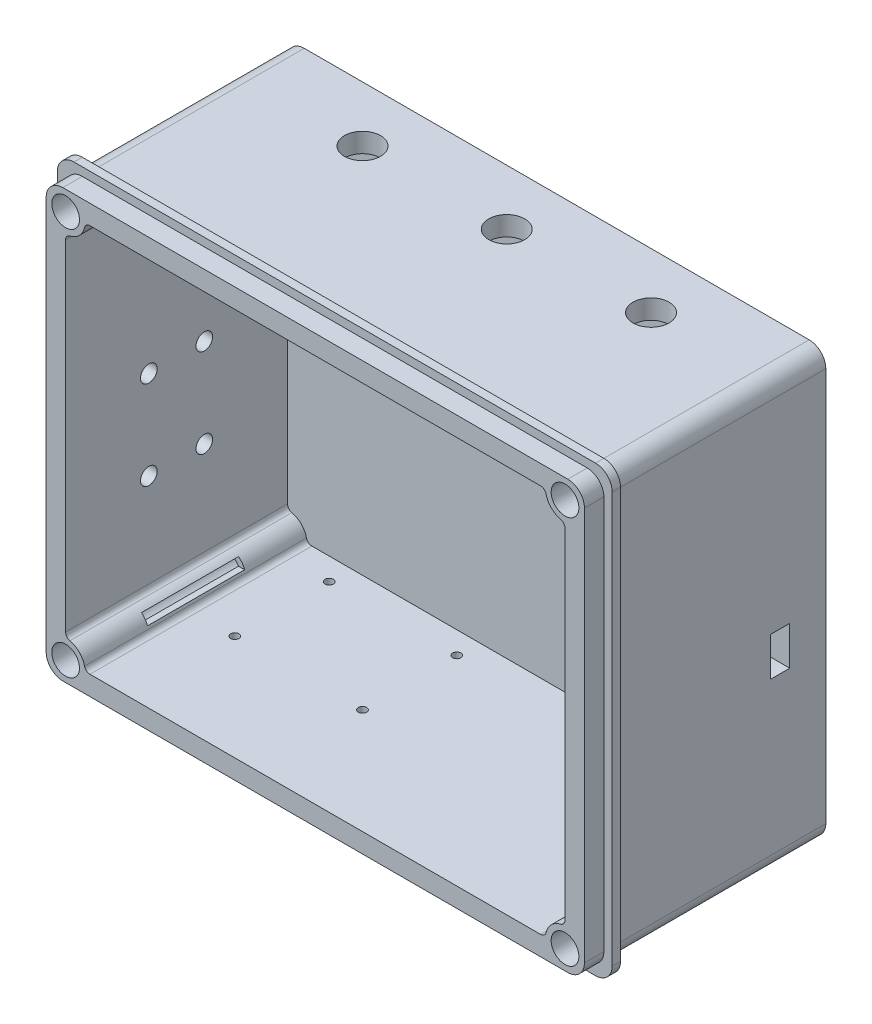
SolidWorks part; units mm, degrees
ref_plane "Plan de face" through (0, 0, 0) normal (0, 0, 1) x (1, 0, 0)
ref_plane "Plan de dessus" through (0, 0, 0) normal (0, 1, 0) x (1, 0, 0)
ref_plane "Plan de droite" through (0, 0, 0) normal (1, 0, 0) x (0, 0, -1)
sketch "Esquisse1" plane through (0, 0, 0) normal (0, 0, 1) x (1, 0, 0)
  line L1 (-90, -70) -> (90, -70)
  line L2 (-90, -70) -> (-90, 70)
  line L3 (-90, 70) -> (90, 70)
  line L4 (90, -70) -> (90, 70)
  line L5 (-90, -70) -> (90, 70) construction
  line L6 (-90, 70) -> (90, -70) construction
  line L7 (-91, -77) -> (91, -77)
  line L8 (-97, -71) -> (-97, 71)
  line L9 (-91, 77) -> (91, 77)
  line L10 (97, -71) -> (97, 71)
  line L11 (-97, -77) -> (97, 77) construction
  line L12 (-97, 77) -> (97, -77) construction
  arc A0 (91, 77) -> (97, 71) centre (91, 71) cw
  arc A1 (91, -77) -> (97, -71) centre (91, -71) ccw
  arc A2 (-91, -77) -> (-97, -71) centre (-91, -71) cw
  arc A3 (-97, 71) -> (-91, 77) centre (-91, 71) cw
  circle A7 centre (90, -70) radius 5
  circle A8 centre (90, 70) radius 5
  circle A9 centre (-90, 70) radius 5
  circle A10 centre (-90, -70) radius 5
  arc A11 (-83, 70) -> (-90, 63) centre (-90, 70) cw
  arc A12 (83, 70) -> (90, 63) centre (90, 70) ccw
  arc A13 (90, -63) -> (83, -70) centre (90, -70) ccw
  arc A14 (-90, -63) -> (-83, -70) centre (-90, -70) cw
  point P0 (0, 0)
  point P6 (0, 0)
  dimension "D5" = 6
  dimension "D6" = 10
  dimension "D7" = 10
  dimension "D8" = 10
  dimension "D9" = 10
  dimension "D10" = 2
  dimension "D11" = 2
  dimension "D12" = 2
  dimension "D13" = 2
  dimension "D1" = 180
  dimension "D2" = 140
  dimension "D3" = 7
  dimension "D4" = 7
extrude "Boss.-Extru.1" add sketch "Esquisse1" against normal blind 7 contours L2 A14 L1 A13 L4 A12 L3 A11 | A3 L8 A2 L7 A1 L10 A0 L9 A10 L2 A9 L3 A8 L4 A7 L1 | A11 L3 A9 L2 | A14 L2 A10 L1 | L4 A13 L1 A7 | L3 A12 L4 A8 region at (-86.1449, -66.1449, 0) region at (0, 0, 0) region at (86.1449, -66.1449, 0) region at (-86.1449, 66.1449, 0) region at (86.1449, 66.1449, 0) region at (-95.0675, -75.0675, 0)
extrude "Boss.-Extru.2" add sketch "Esquisse1<4>" along normal blind 80 contours A11 L3 A9 L2 | A3 L8 A2 L7 A1 L10 A0 L9 A10 L2 A9 L3 A8 L4 A7 L1 | A14 L2 A10 L1 | L4 A13 L1 A7 | L3 A12 L4 A8 region at (-86.1449, -66.1449, 0) region at (86.1449, -66.1449, 0) region at (-86.1449, 66.1449, 0) region at (86.1449, 66.1449, 0) region at (-95.0675, -75.0675, 0)
sketch "Esquisse1<4>" plane through (0, 0, 0) normal (0, 0, 1) x (1, 0, 0) same geometry as "Esquisse1"
fillet "Congé1" radius 2 8 edges at (-90, -63, 40) (-83, -70, 40) (90, -63, 40) (83, -70, 40) (90, 63, 40) (83, 70, 40) (-90, 63, 40) (-83, 70, 40)
sketch "Esquisse2" plane through (0, 0, 0) normal (0, 0, 1) x (1, 0, 0)
  line L0 (90, -61.225) -> (90, 61.225) construction
  line L1 (38, 67) -> (70, 67) construction
  line L2 (38, 67) -> (38, 25) construction
  line L3 (38, 25) -> (70, 25) construction
  line L4 (70, 67) -> (70, 25) construction
  line L5 (-81.225, 70) -> (81.225, 70) construction
  line L6 (41.5, 63.5) -> (66.5, 63.5) construction
  line L7 (41.5, 63.5) -> (41.5, 28.5) construction
  line L8 (41.5, 28.5) -> (66.5, 28.5) construction
  line L9 (66.5, 63.5) -> (66.5, 28.5) construction
  line L10 (28, 90.6353) -> (28, -84.2321) construction
  line L11 (-14, 67) -> (-14, 25) construction
  line L12 (-24, 90.6353) -> (-24, -84.2321) construction
  line L14 (49, 5) -> (87, 5) construction
  line L15 (49, 5) -> (49, -23) construction
  line L16 (49, -23) -> (87, -23) construction
  line L17 (87, 5) -> (87, -23) construction
  line L18 (52.5, 1.5) -> (83.5, 1.5) construction
  line L19 (52.5, 1.5) -> (52.5, -19.5) construction
  line L20 (52.5, -19.5) -> (83.5, -19.5) construction
  line L21 (83.5, 1.5) -> (83.5, -19.5) construction
  circle A0 centre (66.5, 28.5) radius 1.5
  circle A1 centre (66.5, 63.5) radius 1.5
  circle A2 centre (41.5, 63.5) radius 1.5
  circle A3 centre (41.5, 28.5) radius 1.5
  circle A4 centre (-10.5, 28.5) radius 1.5
  circle A5 centre (14.5, 28.5) radius 1.5
  circle A6 centre (-10.5, 63.5) radius 1.5
  circle A7 centre (14.5, 63.5) radius 1.5
  circle A8 centre (-62.5, 28.5) radius 1.5
  circle A9 centre (-37.5, 28.5) radius 1.5
  circle A10 centre (-62.5, 63.5) radius 1.5
  circle A11 centre (-37.5, 63.5) radius 1.5
  circle A12 centre (52.5, 1.5) radius 1.5
  circle A13 centre (83.5, 1.5) radius 1.5
  circle A14 centre (52.5, -19.5) radius 1.5
  circle A15 centre (83.5, -19.5) radius 1.5
  point P30 (-14, 46)
  dimension "D9" = 3
  dimension "D1" = 42
  dimension "D2" = 32
  dimension "D3" = 20
  dimension "D4" = 3.5
  dimension "D5" = 3.5
  dimension "D6" = 3.5
  dimension "D7" = 3.5
  dimension "D8" = 3
  dimension "D10" = 10
  dimension "D11" = 10
  dimension "D12" = 38
  dimension "D13" = 28
  dimension "D14" = 3.5
  dimension "D15" = 3.5
  dimension "D16" = 3.5
  dimension "D17" = 3.5
  dimension "D18" = 3
  dimension "D19" = 20
extrude "Enlèv. mat.-Extru.1" cut sketch "Esquisse2" against normal blind 80
sketch "Esquisse4" plane through (0, 77, 0) normal (0, 1, 0) x (1, 0, 0)
  line L0 (-66, 12.9423) -> (-66, -94.7228) construction
  line L1 (-50, 12.9423) -> (-50, -94.7228) construction
  line L2 (-34, 11.688) -> (-34, -94.7228) construction
  line L4 (-24, 11.688) -> (-24, -94.7228) construction
  line L5 (-91, 7) -> (91, 7) construction
  line L6 (28, 11.688) -> (28, -94.7228) construction
  line L7 (54, 11.688) -> (54, -94.7228) construction
  line L8 (70, 11.688) -> (70, -94.7228) construction
  line L9 (97, 7) -> (97, -80) construction
  circle A0 centre (-50, -13) radius 6.5
  circle A1 centre (2, -13) radius 6.5
  circle A2 centre (54, -13) radius 6.5
  dimension "D5" = 13
  dimension "D1" = 27
  dimension "D2" = 16
  dimension "D3" = 16
  dimension "D4" = 10
  dimension "D6" = 20
  dimension "D7" = 26
  dimension "D8" = 16
extrude "Enlèv. mat.-Extru.2" cut sketch "Esquisse4" against normal blind 10
sketch "Esquisse5" plane through (97, 0, 0) normal (1, 0, 0) x (0, 0, -1)
  line L0 (-91.4794, 5) -> (22.1304, 5) construction
  line L1 (-91.4794, -9) -> (22.1304, -9) construction
  line L2 (-91.4794, -23) -> (22.1304, -23) construction
  line L3 (7, 77) -> (-80, 77) construction
  line L4 (7, -71) -> (7, 71) construction
  line L5 (-13, -16) -> (-6, -16)
  line L6 (-13, -16) -> (-13, -2)
  line L7 (-13, -2) -> (-6, -2)
  line L8 (-6, -16) -> (-6, -2)
  line L9 (-13, -16) -> (-6, -2) construction
  line L10 (-13, -2) -> (-6, -16) construction
  point P8 (-9.5, -9)
  dimension "D1" = 72
  dimension "D2" = 14
  dimension "D3" = 14
  dimension "D4" = 13
  dimension "D5" = 7
  dimension "D6" = 14
extrude "Enlèv. mat.-Extru.3" cut sketch "Esquisse5" against normal blind 10
ref_plane "Plan1" through (-83, 0, 0) normal (1, 0, 0) x (0, 0, -1)
sketch "Esquisse6" plane through (-83, 0, 0) normal (1, 0, 0) x (0, 0, -1)
  line L0 (7, 77) -> (-80, 77) construction
  line L1 (-57, 67.5) -> (-22, 67.5)
  line L2 (-57, 67.5) -> (-57, 64.5)
  line L3 (-57, 64.5) -> (-22, 64.5)
  line L4 (-22, 67.5) -> (-22, 64.5)
  line L5 (-80, 68.4444) -> (-80, 63.175) construction
  line L6 (-90.5523, 0) -> (25.5041, 0) construction
  line L7 (-57, -64.5) -> (-22, -64.5)
  line L8 (-22, -67.5) -> (-22, -64.5)
  line L9 (-57, -67.5) -> (-22, -67.5)
  line L10 (-57, -67.5) -> (-57, -64.5)
  dimension "D1" = 3
  dimension "D2" = 35
  dimension "D3" = 9.5
  dimension "D4" = 23
extrude "Enlèv. mat.-Extru.4" cut sketch "Esquisse6" against normal up to surface (7 mm away) up to face at (-90, 0, 40)
ref_plane "Plan2" through (0, -63, 0) normal (0, 1, 0) x (1, 0, 0)
sketch "Esquisse7" plane through (0, -63, 0) normal (0, 1, 0) x (1, 0, 0)
  line L1 (84.5, -22) -> (87.5, -22)
  line L2 (84.5, -22) -> (84.5, -57)
  line L3 (84.5, -57) -> (87.5, -57)
  line L4 (87.5, -22) -> (87.5, -57)
  line L5 (97, 7) -> (97, -80) construction
  line L6 (-85.6699, -22) -> (-83.4617, -22) construction
  dimension "D1" = 9.5
  dimension "D2" = 3
  dimension "D3" = 35
extrude "Enlèv. mat.-Extru.5" cut sketch "Esquisse7" against normal up to surface (7 mm away) up to face at (0, -70, 40)
sketch "Esquisse8" plane through (0, -70, 0) normal (0, 1, 0) x (1, 0, 0)
  line L0 (-97, 7) -> (-97, -80) construction
  line L5 (-67, -8) -> (-21, -8)
  line L6 (-67, -8) -> (-67, -42)
  line L7 (-67, -42) -> (-21, -42)
  line L8 (-21, -8) -> (-21, -42)
  line L9 (-91, 7) -> (91, 7) construction
  circle A0 centre (-67, -8) radius 1.5
  circle A1 centre (-21, -8) radius 1.5
  circle A2 centre (-21, -42) radius 1.5
  circle A3 centre (-67, -42) radius 1.5
  dimension "D5" = 3
  dimension "D1" = 34
  dimension "D2" = 46
  dimension "D3" = 30
  dimension "D4" = 15
extrude "Enlèv. mat.-Extru.6" cut sketch "Esquisse8" against normal blind 10 contours L6 A3 L7 | L7 A3 L6 | L6 A0 L5 | L5 A0 L6 | L5 A1 L8 | L8 A1 L5 | L7 A2 L8 | L8 A2 L7 region at (-67.2122, -70, 7.7878) region at (-66.3634, -70, 8.6366) region at (-20.7878, -70, 7.7878) region at (-21.6366, -70, 8.6366) region at (-66.3634, -70, 41.3634) region at (-67.2122, -70, 42.2122) region at (-20.7878, -70, 42.2122) region at (-21.6366, -70, 41.3634)
sketch "Esquisse10" plane through (0, 0, 0) normal (0, 0, 1) x (1, 0, 0)
  line L0 (-91, 77) -> (91, 77) construction
  line L1 (-94, -80) -> (94, -80)
  line L2 (-100, -74) -> (-100, 74)
  line L3 (-94, 80) -> (94, 80)
  line L4 (100, -74) -> (100, 74)
  line L5 (-100, -80) -> (100, 80) construction
  line L6 (-100, 80) -> (100, -80) construction
  line L8 (-91, -77) -> (91, -77) construction
  line L9 (97, -71) -> (97, 71) construction
  line L11 (-91, -77) -> (91, -77)
  line L12 (-97, -71) -> (-97, 71)
  line L13 (-91, 77) -> (91, 77)
  line L14 (97, -71) -> (97, 71)
  line L15 (-97, -77) -> (97, 77) construction
  line L16 (-97, 77) -> (97, -77) construction
  arc A0 (91, 77) -> (97, 71) centre (91, 71) cw
  arc A1 (91, -77) -> (97, -71) centre (91, -71) ccw
  arc A2 (-91, -77) -> (-97, -71) centre (-91, -71) cw
  arc A3 (-97, 71) -> (-91, 77) centre (-91, 71) cw
  arc A4 (94, 80) -> (100, 74) centre (94, 74) cw
  arc A5 (94, -80) -> (100, -74) centre (94, -74) ccw
  arc A6 (-94, -80) -> (-100, -74) centre (-94, -74) cw
  arc A7 (-100, 74) -> (-94, 80) centre (-94, 74) cw
  point P0 (0, 0)
  point P10 (0, 0)
  dimension "D3" = 6
  dimension "D1" = 3
  dimension "D2" = 3
extrude "Boss.-Extru.3" add sketch "Esquisse10" along normal blind 3 from offset 70
fillet "Congé2" radius 2 8 edges at (-95.2426, 75.2426, 70) (0, 77, 70) (95.2426, 75.2426, 70) (97, 0, 70) (95.2426, -75.2426, 70) (0, -77, 70) (-95.2426, -75.2426, 70) (-97, 0, 70)
sketch "Esquisse11" plane through (-90, 0, 0) normal (1, 0, 0) x (0, 0, -1)
  line L0 (-80, -61.225) -> (-80, 61.225) construction
  line L1 (-50, -27.5) -> (-30, -27.5) construction
  line L2 (-50, -27.5) -> (-50, 4.5) construction
  line L3 (-50, 4.5) -> (-30, 4.5) construction
  line L4 (-30, -27.5) -> (-30, 4.5) construction
  line L5 (-50, -27.5) -> (-30, 4.5) construction
  line L6 (-50, 4.5) -> (-30, -27.5) construction
  line L7 (7, 77) -> (-68, 77) construction
  circle A0 centre (-50, -27.5) radius 3
  circle A1 centre (-50, 4.5) radius 3
  circle A2 centre (-30, 4.5) radius 3
  circle A3 centre (-30, -27.5) radius 3
  point P0 (-40, -11.5)
  dimension "D4" = 6
  dimension "D1" = 32
  dimension "D2" = 20
  dimension "D3" = 30
  dimension "D5" = 72.5
extrude "Enlèv. mat.-Extru.7" cut sketch "Esquisse11" against normal blind 10
equation "\"èà\"=0"
equation "\"éà\"=23"
